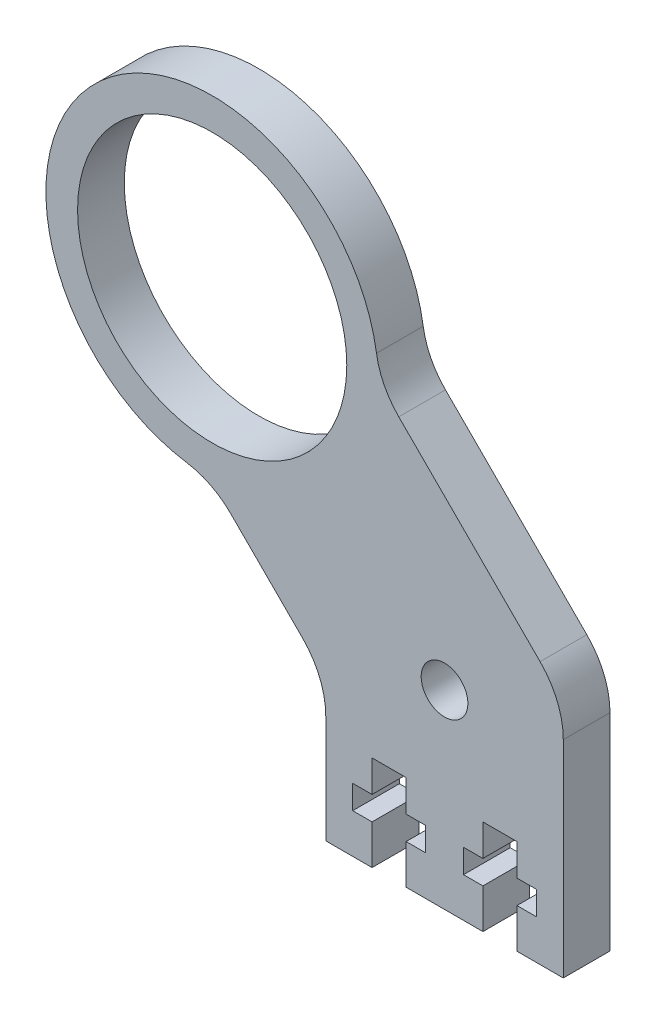
SolidWorks part; units mm, degrees
ref_plane "Front Plane" through (0, 0, 0) normal (0, 0, 1) x (1, 0, 0)
ref_plane "Top Plane" through (0, 0, 0) normal (0, 1, 0) x (1, 0, 0)
ref_plane "Right Plane" through (0, 0, 0) normal (1, 0, 0) x (0, 0, -1)
sketch "Sketch1" plane through (0, 0, 0) normal (0, 0, 1) x (1, 0, 0)
  line L0 (0, 0) -> (-29.3449, 29.3449) construction
  line L1 (0, 0) -> (0, 31.0325) construction
  line L2 (-15, -6.2132) -> (-15, -24)
  line L3 (-15, -24) -> (15, -24)
  line L4 (15, -24) -> (15, 6.2132)
  line L5 (0, 0) -> (0, -24) construction
  line L6 (15, 6.2132) -> (-8.346, 29.5592)
  line L7 (-15, -6.2132) -> (-29.5592, 8.346)
  line L8 (10.6066, 10.6066) -> (-18.7383, 39.9515) construction
  line L9 (-10.6066, -10.6066) -> (-39.9515, 18.7383) construction
  circle A0 centre (0, 0) radius 2.95
  arc A1 (-8.346, 29.5592) -> (-29.5592, 8.346) centre (-29.3449, 29.3449) ccw
  dimension "D1" = 5.9
  dimension "D3" = 42
  dimension "D2" = 41.5
  dimension "D4" = 45
  dimension "D5" = 24
  dimension "D6" = 30
  dimension "D7" = 15
  dimension "D8" = 15
extrude "Boss-Extrude1" add sketch "Sketch1" along normal blind 5.9
sketch "Sketch2" plane through (0, 0, 5.9) normal (0, 0, 1) x (1, 0, 0)
  circle A0 centre (-29.3449, 29.3449) radius 17
  dimension "D1" = 34
extrude "Cut-Extrude1" cut sketch "Sketch2" against normal through all
sketch "Sketch3" plane through (0, 0, 5.9) normal (0, 0, 1) x (1, 0, 0)
  line L0 (-15, -24) -> (15, -24) construction
  line L1 (-9.15, -24) -> (-4.85, -24)
  line L2 (-9.15, -24) -> (-9.15, -19)
  line L3 (-9.15, -12) -> (-4.85, -12)
  line L4 (-4.85, -24) -> (-4.85, -19)
  line L5 (0, 0) -> (0, -24) construction
  line L6 (-4.85, -16) -> (-2.4, -16)
  line L7 (-11.6, -16) -> (-9.15, -16)
  line L8 (-11.6, -16) -> (-11.6, -19)
  line L9 (-11.6, -19) -> (-9.15, -19)
  line L10 (-2.4, -16) -> (-2.4, -19)
  line L11 (-9.15, -16) -> (-9.15, -12)
  line L12 (-4.85, -19) -> (-2.4, -19)
  line L13 (-4.85, -16) -> (-4.85, -12)
  line L14 (4.85, -16) -> (4.85, -12)
  line L15 (4.85, -19) -> (2.4, -19)
  line L16 (9.15, -16) -> (9.15, -12)
  line L17 (2.4, -16) -> (2.4, -19)
  line L18 (11.6, -19) -> (9.15, -19)
  line L19 (11.6, -16) -> (11.6, -19)
  line L20 (11.6, -16) -> (9.15, -16)
  line L21 (4.85, -16) -> (2.4, -16)
  line L22 (4.85, -24) -> (4.85, -19)
  line L23 (9.15, -12) -> (4.85, -12)
  line L24 (9.15, -24) -> (9.15, -19)
  line L25 (9.15, -24) -> (4.85, -24)
  point P6 (-7, -12)
  point P18 (-10.375, -19)
  dimension "D1" = 4.3
  dimension "D2" = 7
  dimension "D3" = 12
  dimension "D4" = 9.2
  dimension "D5" = 3
  dimension "D6" = 5
extrude "Cut-Extrude2" cut sketch "Sketch3" against normal through all
fillet "Fillet1" radius 10 4 edges at (-15, -6.2132, 2.95) (15, 6.2132, 2.95) (-29.5592, 8.346, 2.95) (-8.346, 29.5592, 2.95)
equation "\"smallPulleyTeeth\"= 15"
equation "\"largePulleyTeeth\"= 40"
equation "\"eighthThick\"= 2.9mm"
equation "\"sixteenthThick\" = 1.7mm"
equation "\"quarterThick\"=5.9mm"
equation "\"OD\" = 145mm"
equation "\"puckAngle\" = 60.5deg"
equation "\"puckDiam\" = 76.5mm"
equation "\"axlePress\" = 5.9mm"
equation "\"D1@Sketch1\"=\"axlePress\""
equation "\"D1@Boss-Extrude1\"=\"quarterThick\""
equation "\"press\" = 0.2mm"
equation "\"wheelClear\" = 0.3mm"
equation "\"10-32clear\" = 4.5mm"
equation "\"D1@Sketch3\"=\"10-32clear\" - \"press\""
equation "\"6-32clear\" = 3.3mm"
equation "\"8-32clear\" = 4.0mm"
equation "\"wheelHeight\" = 24mm"
equation "\"D5@Sketch1\"=\"wheelHeight\""
